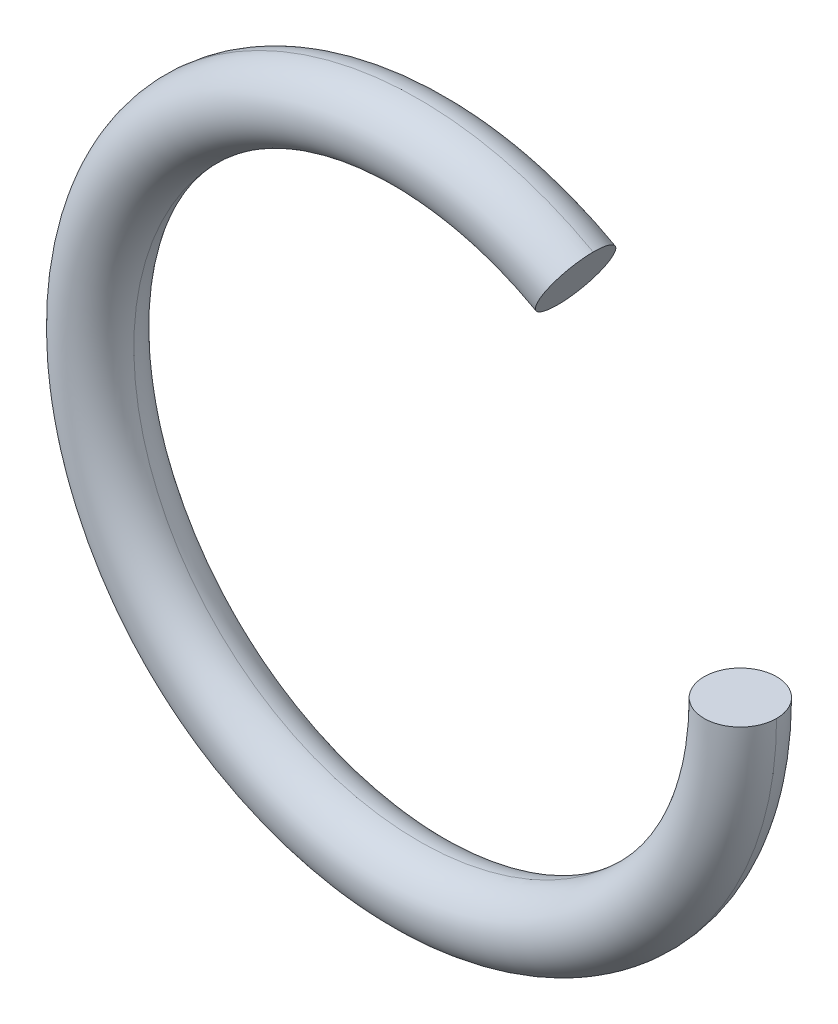
SolidWorks part; units mm, degrees
ref_plane "Front" through (0, 0, 0) normal (0, 0, 1) x (1, 0, 0)
ref_plane "Top" through (0, 0, 0) normal (0, 1, 0) x (1, 0, 0)
ref_plane "Right" through (0, 0, 0) normal (1, 0, 0) x (0, 0, -1)
sketch "Sketch1" plane through (0, 0, 0) normal (0, 0, 1) x (1, 0, 0)
  line L0 (0, 0) -> (28.3513, 0) construction
  line L1 (0, 0) -> (0, 38.0466) construction
  line L2 (0, 0) -> (3.5614, 6.3826) construction
  arc A0 (1.9247, 3.4494) -> (3.95, 0) centre (0, 0) ccw
  dimension "d5" = 7.9
  dimension "e" = 4
sketch "Sketch2" plane through (0, 0, 0) normal (0, 1, 0) x (1, 0, 0)
  circle A0 centre (3.55, 0) radius 0.4
  point P2 (3.95, 0)
  dimension "d4" = 0.8
sweep "Sweep1" add profiles "Sketch2" path "Sketch1"
split line "Split Line1"
